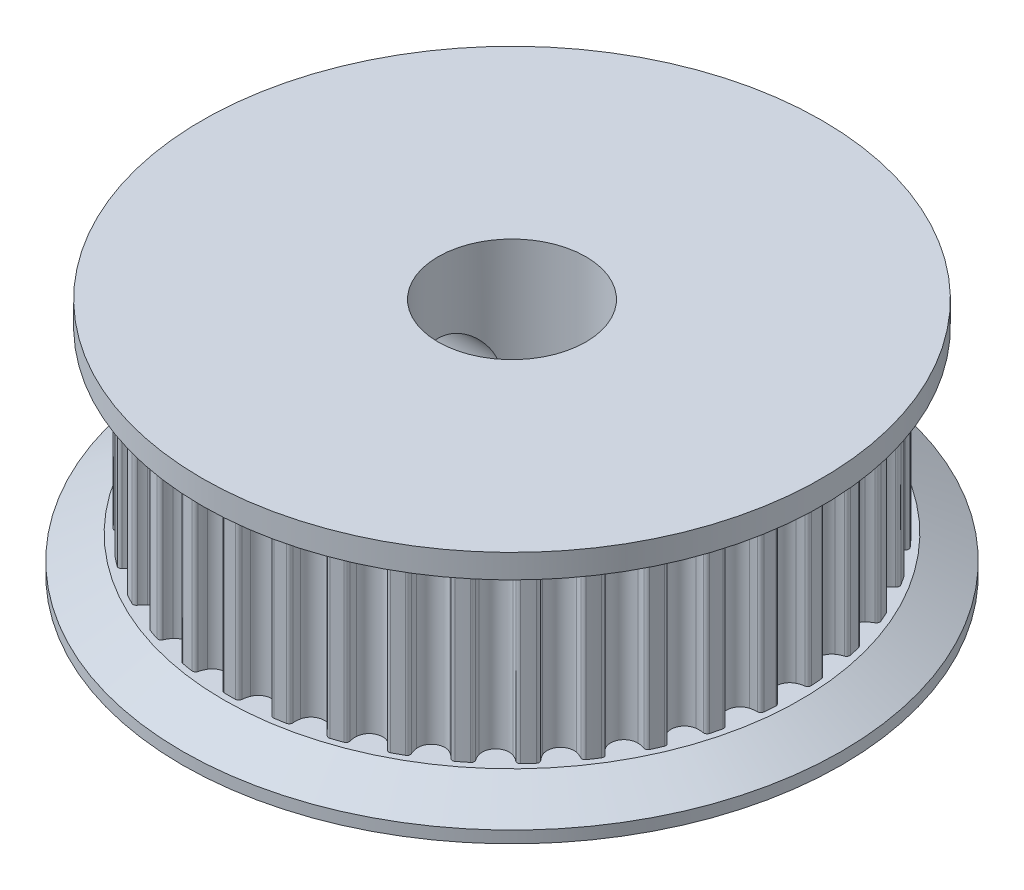
SolidWorks part; units mm, degrees
ref_plane "Front" through (0, 0, 0) normal (0, 0, 1) x (1, 0, 0)
ref_plane "Top" through (0, 0, 0) normal (0, 1, 0) x (1, 0, 0)
ref_plane "Right" through (0, 0, 0) normal (1, 0, 0) x (0, 0, -1)
sketch "Sketch1" plane through (0, 0, 0) normal (0, 1, 0) x (1, 0, 0)
  line L0 (0, 0) -> (0, 12.0958) construction
  line L1 (0, 11.8418) -> (0, 12.4718)
  line L2 (0, 0) -> (0.9989, 12.0545) construction
  line L3 (1.9491, 11.6803) -> (2.0528, 12.3017)
  line L4 (1.3765, 11.7685) -> (1.4052, 12.0139) construction
  arc A0 (0.2321, 11.8395) -> (0.3788, 11.6998) centre (0.2292, 11.6895) cw
  arc A1 (0.3788, 11.6998) -> (0.4446, 11.4056) centre (1.3765, 11.7685) ccw
  circle A2 centre (0, 0) radius 12.0958 construction
  arc A3 (0.2321, 11.8395) -> (0, 11.8418) centre (0, 0) ccw
  arc A4 (0.916, 11.0539) -> (0, 11.0918) centre (0, 0) ccw construction
  arc A5 (0.4446, 11.4056) -> (1.4388, 11.3232) centre (0.9618, 11.607) ccw
  arc A6 (1.3765, 11.7685) -> (0.9785, 11.8082) centre (0, 0) ccw construction
  arc A7 (0, 12.4718) -> (2.0528, 12.3017) centre (0, 0) cw
  arc A8 (1.5521, 11.6026) -> (1.4388, 11.3232) centre (0.5793, 11.8345) cw
  arc A9 (1.7198, 11.7162) -> (1.5521, 11.6026) centre (1.698, 11.5678) ccw
  arc A10 (1.7198, 11.7162) -> (1.9491, 11.6803) centre (0, 0) cw
  dimension "D1" = 0.15
  dimension "D4" = 24.1916
  dimension "D5" = 1
  dimension "D7" = 0.555
  dimension "D3" = 4.737
  dimension "D8" = 0.75
  dimension "D6" = 0.254
  dimension "D2" = 0.4
  dimension "D9" = 1.38
  dimension "D11" = 0.4083
  dimension "D12" = 0.2471
  dimension "D10" = 1.934
sketch "Sketch2" plane through (0, 0, 0) normal (0, 1, 0) x (1, 0, 0)
  circle A0 centre (0, 0) radius 12.0958 construction
  circle A1 centre (0, 0) radius 12.0958
  circle A2 centre (0, 0) radius 3.1
  dimension "D1" = 6.2
extrude "Boss-Extrude1" add sketch "Sketch2" along normal mid plane 10
sketch "Sketch6" plane through (0, 0, 0) normal (0, 1, 0) x (1, 0, 0)
  line L0 (0, 11.8318) -> (0, 12.4718)
  line L1 (1.9474, 11.6704) -> (2.0528, 12.3017)
  arc A7 (2.0528, 12.3017) -> (0, 12.4718) centre (0, 0) ccw construction
  arc A8 (2.0528, 12.3017) -> (0, 12.4718) centre (0, 0) ccw
  arc A14 (1.7183, 11.7063) -> (1.5618, 11.6003) centre (1.698, 11.5678) ccw
  arc A15 (1.4474, 11.3181) -> (1.5618, 11.6003) centre (0.5793, 11.8345) ccw
  arc A16 (0.4353, 11.402) -> (1.4474, 11.3181) centre (0.9618, 11.607) ccw
  arc A17 (0.3688, 11.6991) -> (0.4353, 11.402) centre (1.3765, 11.7685) ccw
  arc A18 (0.3688, 11.6991) -> (0.2319, 11.8295) centre (0.2292, 11.6895) ccw
  arc A19 (0.2319, 11.8295) -> (0, 11.8318) centre (0, 0) ccw
  arc A20 (1.9474, 11.6704) -> (1.7183, 11.7063) centre (0, 0) ccw
  arc A21 (1.7183, 11.7063) -> (1.5618, 11.6003) centre (1.698, 11.5678) ccw
  arc A22 (1.4474, 11.3181) -> (1.5618, 11.6003) centre (0.5793, 11.8345) ccw
  arc A23 (0.4353, 11.402) -> (1.4474, 11.3181) centre (0.9618, 11.607) ccw
  arc A24 (0.3688, 11.6991) -> (0.4353, 11.402) centre (1.3765, 11.7685) ccw
  arc A25 (0.3688, 11.6991) -> (0.2319, 11.8295) centre (0.2292, 11.6895) ccw
  arc A26 (0.2319, 11.8295) -> (0, 11.8318) centre (0, 0) ccw
  arc A27 (1.9474, 11.6704) -> (1.7183, 11.7063) centre (0, 0) ccw
extrude "Cut-Extrude3" cut sketch "Sketch6" against normal through all both and the other way through all
pattern_circular "CirPattern3" count 38 over 360 about axis through (0, 5, 0) along (0, -1, 0) of "Cut-Extrude3"
sketch "Sketch3" plane through (0, 0, 0) normal (0, 0, 1) x (1, 0, 0)
  line L0 (0, 0) -> (0, 9.5108) construction
  line L1 (-12.0958, 5) -> (-13.8278, 6)
  line L2 (-13.8278, 6) -> (-13.8278, 6.5)
  line L3 (-13.8278, 6.5) -> (-3.1, 6.5)
  line L4 (-3.1, 6.5) -> (-3.1, 5)
  line L5 (-3.1, 5) -> (-12.0958, 5)
  line L6 (3.1, 5) -> (-3.1, 5) construction
  dimension "D4" = 24.1916
  dimension "D1" = 1.5
  dimension "D2" = 0.5
  dimension "D3" = 30
revolve "Revolve1" add sketch "Sketch3" angle 360 about L0
mirror "Mirror1" about plane through (0, 0, 0) normal (0, 1, 0) of "Revolve1"
sketch "Sketch4" plane through (0, 0, 0) normal (0, 0, 1) x (1, 0, 0)
  line L0 (0, 0) -> (0, 14.0175) construction
  line L1 (13.8278, 6.5) -> (-13.8278, 6.5) construction
  line L2 (-3.1, 6.5) -> (-9.6, 6.5)
  line L3 (-3.1, 6.5) -> (-3.1, 12.5)
  line L4 (-3.1, 12.5) -> (-9.6, 12.5)
  line L5 (-9.6, 6.5) -> (-9.6, 12.5)
  dimension "D2" = 6
  dimension "D1" = 6.5
revolve "Revolve2" add sketch "Sketch4" angle 360 about L0
sketch "Sketch5" plane through (0, 0, 0) normal (0, 0, 1) x (1, 0, 0)
  line L1 (0, 6.5) -> (0, 12.5) construction
  line L2 (9.6, 12.5) -> (-9.6, 12.5) construction
  line L7 (-9.6, 12.5) -> (-9.6, 6.5) construction
  line L8 (-9.6, 12.5) -> (-9.6, 6.5) construction
  circle A0 centre (0, 9.5) radius 1.6
  dimension "D1" = 3.2
extrude "Cut-Extrude2" cut sketch "Sketch5" along normal through all
pattern_circular "CirPattern2" count 2 over 90 about axis through (0, 5, 0) along (0, -1, 0) of "Cut-Extrude2" reverse direction yes
sketch "Sketch7" plane through (0, 12.5, 0) normal (0, 1, 0) x (1, 0, 0)
  circle A0 centre (0, 0) radius 18
extrude "Cut-Extrude4" cut sketch "Sketch7" against normal blind 10
sketch "Sketch8" plane through (0, 0, 0) normal (1, 0, 0) x (0, 0, -1)
  circle A0 centre (0, -1.4146) radius 1.95
  dimension "D1" = 3.9
extrude "Cut-Extrude5" cut sketch "Sketch8" against normal through all
sketch "Sketch10" plane through (0, 0, 0) normal (1, 0, 0) x (0, 0, -1)
  circle A0 centre (0, -1.4146) radius 2.75
  dimension "D1" = 5.5
extrude "Cut-Extrude6" cut sketch "Sketch10" against normal blind 10 from offset 8 offset against normal yes
sketch "Sketch11" plane through (0, 2.5, 0) normal (0, 1, 0) x (1, 0, 0)
  circle A0 centre (0, 0) radius 13
  dimension "D1" = 26
extrude "Boss-Extrude3" add sketch "Sketch11" along normal blind 1
sketch "Sketch12" plane through (0, 3.5, 0) normal (0, 1, 0) x (1, 0, 0)
  circle A0 centre (0, 0) radius 3.1
  dimension "D1" = 6.2
extrude "Cut-Extrude7" cut sketch "Sketch12" against normal blind 10
equation "\"belt-step\"= 2"
equation "\"pulley-teeth\"= 38"
equation "\"pulley-dia\"= ( \"belt-step\" * \"pulley-teeth\" ) / Pi"
equation "\"D3@Sketch1\"=(360/\"pulley-teeth\")/2"
equation "\"D4@Sketch1\"=\"pulley-dia\""
equation "\"bore-dia\"= 6.2"
equation "\"belt-thick\"= 10"
equation "\"D4@Sketch3\"=\"pulley-dia\""
equation "\"D1@Sketch2\"=\"bore-dia\""
equation "\"D1@Boss-Extrude1\"=\"belt-thick\""
equation "\"teeth-offset\"= 0.01"
equation "\"D1@Sketch6\"=\"teeth-offset\""
equation "\"D1@CirPattern3\"=\"pulley-teeth\""
equation "\"flange-wall\"= 6.5"
equation "\"D1@Sketch4\"=\"flange-wall\""
equation "\"flange-h\"= 6"
equation "\"screw-dia\"= 3.2"
equation "\"D2@Sketch4\"=\"flange-h\""
equation "\"D1@Sketch5\"=\"screw-dia\""
equation "\"D10@Sketch1\"=(0.4/(Pi*(\"pulley-dia\"-(2*\"D12@Sketch1\"))))*360"
